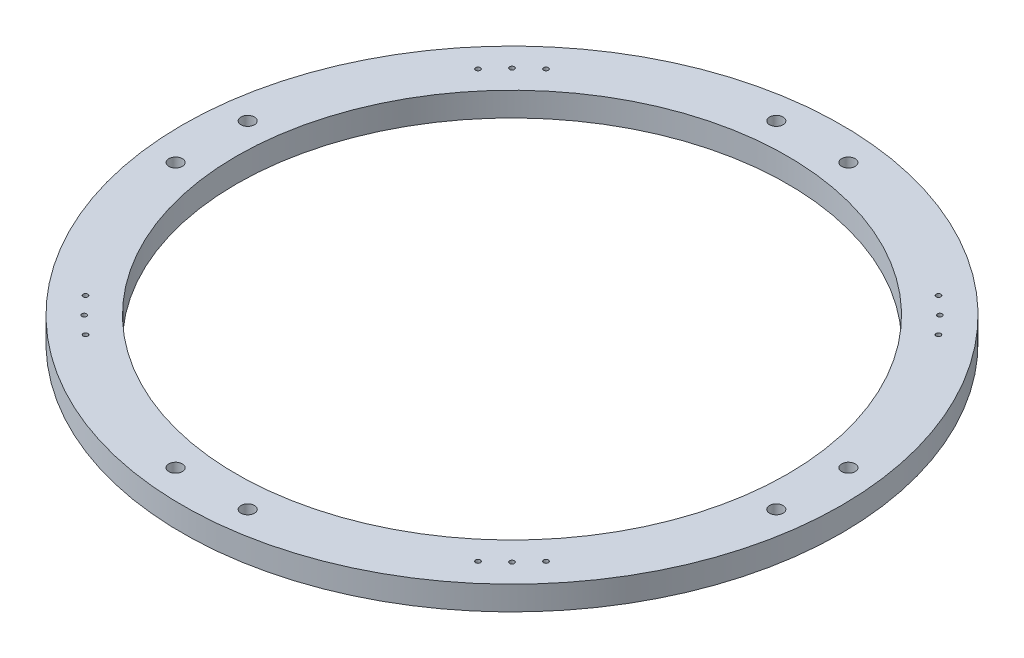
SolidWorks part; units mm, degrees
material "Oak"
ref_plane "Front Plane" through (0, 0, 0) normal (0, 0, 1) x (1, 0, 0)
ref_plane "Top Plane" through (0, 0, 0) normal (0, 1, 0) x (1, 0, 0)
ref_plane "Right Plane" through (0, 0, 0) normal (1, 0, 0) x (0, 0, -1)
sketch "Sketch1" plane through (0, 0, 0) normal (0, 0, 1) x (1, 0, 0)
  line L0 (0, -200000) -> (0, 218797.9879) construction
  line L5 (0, -200000) -> (0, 218797.9879) construction
  line L6 (174.1012, 209.4005) -> (174.1012, 196.7005)
  line L7 (145.5262, 209.4005) -> (174.1012, 209.4005)
  line L8 (174.1012, 196.7005) -> (145.5262, 196.7005)
  line L9 (145.5262, 196.7005) -> (145.5262, 209.4005)
revolve "Revolve1" add sketch "Sketch1" angle 360 about L5
hole_wizard "Tap Drill for M3x0.5 Tap1" positions "Sketch5" profile "Sketch6" hole size "M3x0.5" standard "ANSI Metric" end condition through all
sketch "Sketch5" plane through (0, 209.4005, 0) normal (0, 1, 0) x (1, 0, 0)
  line L0 (0, 0) -> (-113.0054, 113.0054) construction
  point P0 (-113.0054, 113.0054)
  point P3 (-103.6677, 121.6282)
  point P6 (-121.6282, 103.6677)
  dimension "D1" = 159.8137
sketch "Sketch6" plane through (-113.0054, 209.4005, -113.0054) normal (1, 0, 0) x (0, 0, 1)
  line L0 (0, 0) -> (0, 12.7)
  line L1 (0, 12.7) -> (1.25, 12.7)
  line L2 (1.25, 12.7) -> (1.25, 0)
  line L5 (1.25, 0) -> (0, 0)
  line L11 (0, -6.35) -> (0, 107.95) construction
  dimension "Thru Hole Dia." = 2.5
  dimension "Thru Hole Depth" = 12.7
sketch "Sketch7" plane through (0, 209.4005, 0) normal (0, 1, 0) x (1, 0, 0)
  line L0 (0, 0) -> (158.6742, 0) construction
  line L1 (158.6742, 19.05) -> (158.6742, -19.05) construction
  line L2 (158.6742, -19.05) -> (0, 0) construction
  line L3 (0, 0) -> (158.6742, 19.05) construction
  circle A0 centre (158.6742, -19.05) radius 3.5719
  circle A1 centre (158.6742, 19.05) radius 3.5719
  point P6 (158.6742, 0)
  dimension "D3" = 7.1437
  dimension "D1" = 38.1
  dimension "D2" = 159.8137
extrude "Cut-Extrude1" cut sketch "Sketch7" against normal through all
pattern_circular "CirPattern1" count 4 over 360 about axis through (0, -200000, 0) along (0, -1, 0) of "Tap Drill for M3x0.5 Tap1", "Cut-Extrude1"
